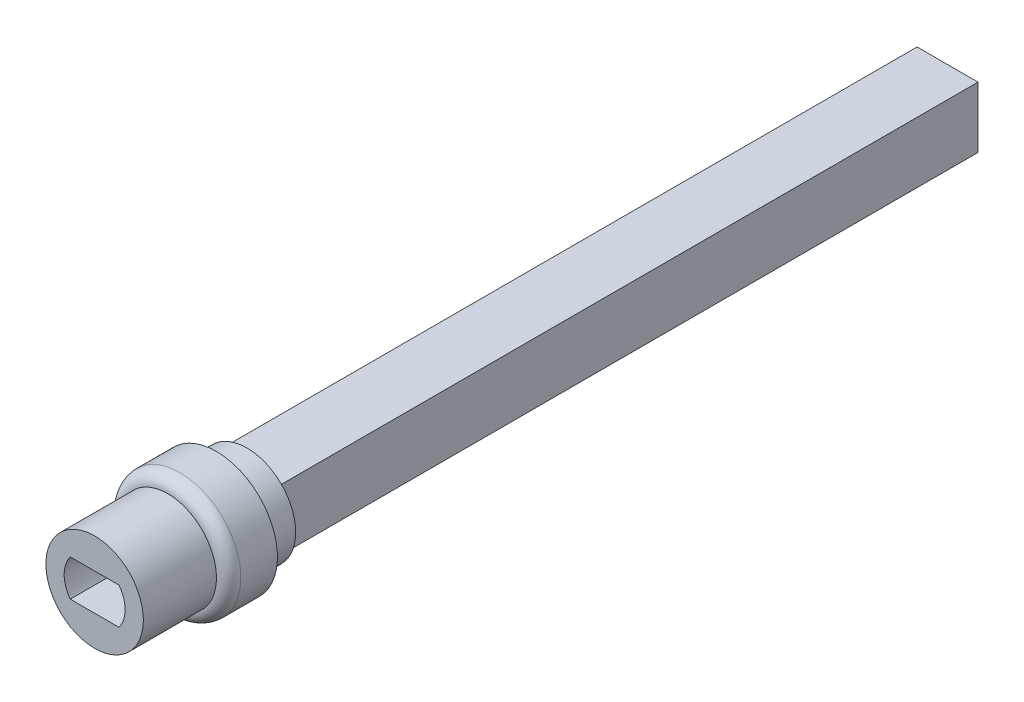
SolidWorks part; units mm, degrees
material "ABS"
ref_plane "Plan de face" through (0, 0, 0) normal (0, 0, 1) x (1, 0, 0)
ref_plane "Plan de dessus" through (0, 0, 0) normal (0, 1, 0) x (1, 0, 0)
ref_plane "Plan de droite" through (0, 0, 0) normal (1, 0, 0) x (0, 0, -1)
sketch "Esquisse1" plane through (0, 0, 0) normal (0, 0, 1) x (1, 0, 0)
  line L0 (-2, 1.5) -> (2, 1.5)
  line L1 (-2, -1.5) -> (2, -1.5)
  line L2 (0, 1.5) -> (0, -1.5) construction
  circle A0 centre (0, 0) radius 4
  arc A1 (-2, 1.5) -> (-2, -1.5) centre (0, 0) ccw
  arc A2 (2, -1.5) -> (2, 1.5) centre (0, 0) ccw
  point P10 (0, 0)
  point P11 (3.4573, -3.2652)
  point P12 (3.7866, 1.8933)
  point P13 (0, 0)
  dimension "D1" = 2.5
  dimension "D3" = 8
  dimension "D2" = 3
extrude "Boss.-Extru.1" add sketch "Esquisse1" along normal blind 6
sketch "Esquisse2" plane through (0, 0, 0) normal (0, 0, -1) x (-1, 0, 0)
  circle A0 centre (0, 0) radius 5
  dimension "D1" = 10
extrude "Boss.-Extru.2" add sketch "Esquisse2" along normal blind 4
fillet "Congé1" radius 1 1 edges at (-5, 0, 0)
sketch "Esquisse3" plane through (0, 0, -4) normal (0, 0, -1) x (-1, 0, 0)
  line L1 (2.5, -2.5) -> (-2.5, -2.5)
  line L2 (2.5, -2.5) -> (2.5, 2.5)
  line L3 (2.5, 2.5) -> (-2.5, 2.5)
  line L4 (-2.5, -2.5) -> (-2.5, 2.5)
  line L5 (2.5, -2.5) -> (-2.5, 2.5) construction
  line L6 (2.5, 2.5) -> (-2.5, -2.5) construction
  point P0 (0, 0)
  dimension "D1" = 5
extrude "Boss.-Extru.3" add sketch "Esquisse3" along normal blind 60
sketch "Esquisse4" plane through (0, 0, -4) normal (0, 0, -1) x (-1, 0, 0)
  circle A0 centre (0, 0) radius 4
  dimension "D1" = 8
extrude "Boss.-Extru.4" add sketch "Esquisse4" along normal blind 2.5
